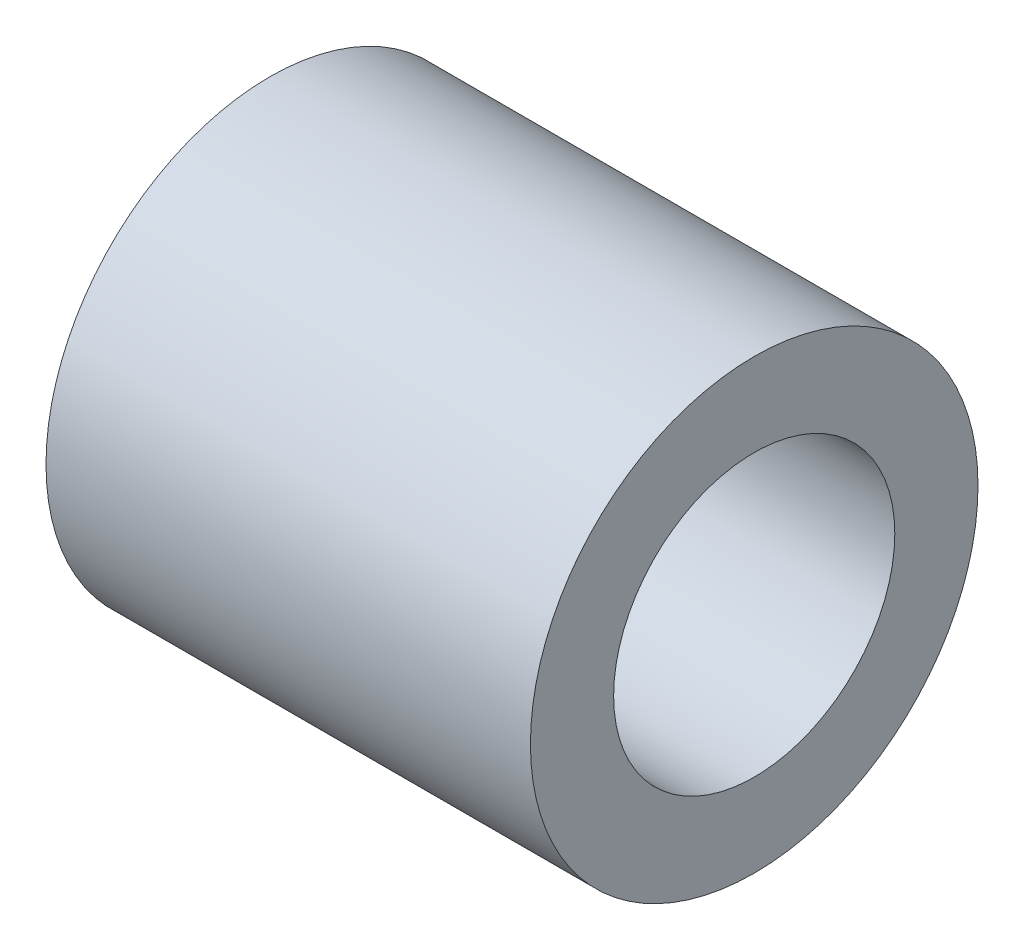
SolidWorks part; units mm, degrees
material "PLA"
ref_plane "Front Plane" through (0, 0, 0) normal (0, 0, 1) x (1, 0, 0)
ref_plane "Top Plane" through (0, 0, 0) normal (0, 1, 0) x (1, 0, 0)
ref_plane "Right Plane" through (0, 0, 0) normal (1, 0, 0) x (0, 0, -1)
sketch "Sketch1" plane through (0, 0, 0) normal (1, 0, 0) x (0, 0, -1)
  circle A0 centre (0, 0) radius 3.3909
  circle A1 centre (0, 0) radius 5.3975
  dimension "D1" = 6.7818
  dimension "D2" = 10.795
extrude "Boss-Extrude1" add sketch "Sketch1" along normal blind 11.684
